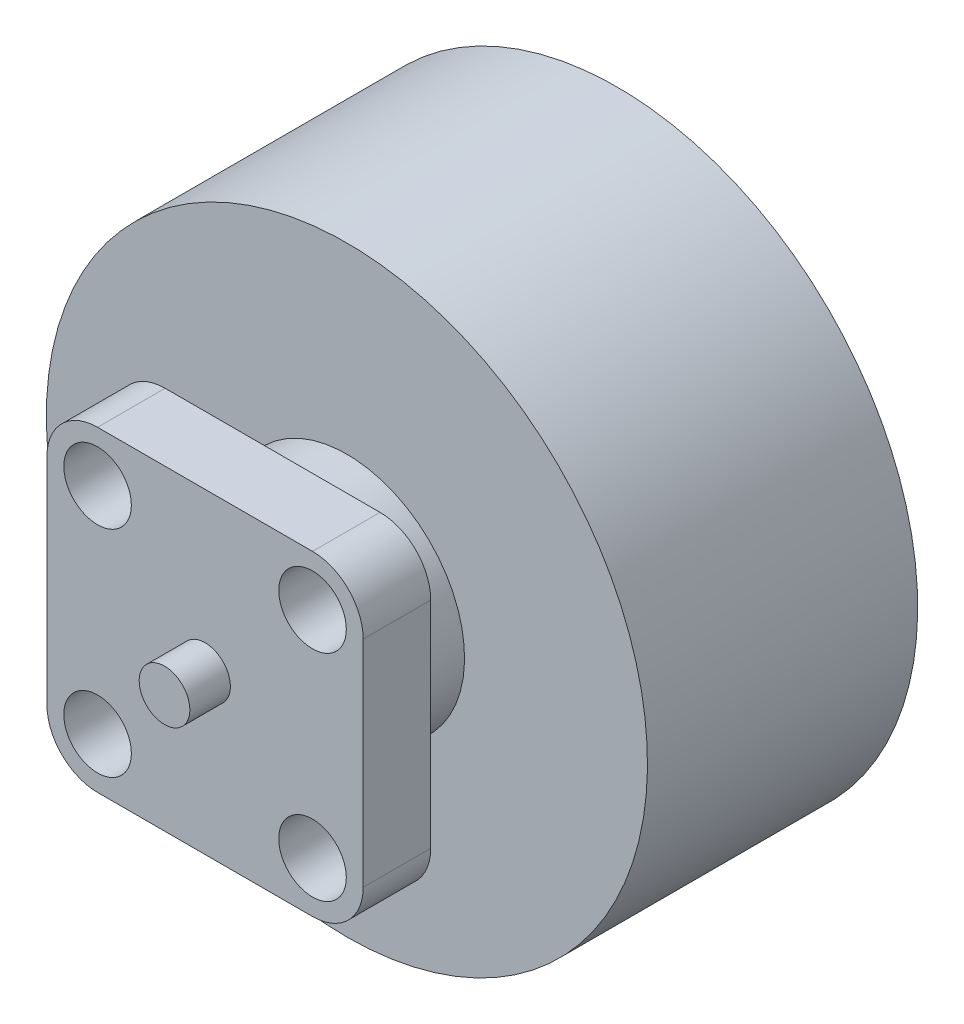
SolidWorks part; units mm, degrees
ref_plane "Front Plane" through (0, 0, 0) normal (0, 0, 1) x (1, 0, 0)
ref_plane "Top Plane" through (0, 0, 0) normal (0, 1, 0) x (1, 0, 0)
ref_plane "Right Plane" through (0, 0, 0) normal (1, 0, 0) x (0, 0, -1)
sketch "Sketch1" plane through (0, 0, 0) normal (1, 0, 0) x (0, 0, -1)
  line L0 (-1.2, 0) -> (16.4, 0)
  line L2 (-1.2, 0.75) -> (16.4, 0.75)
  line L3 (-1.2, 0.75) -> (-1.2, -0.75)
  line L4 (-1.2, -0.75) -> (16.4, -0.75)
  line L5 (16.4, 0.75) -> (16.4, -0.75)
  line L6 (4.2, 0) -> (12.2, 0)
  line L7 (4.2, 0) -> (4.2, 8.9)
  line L8 (4.2, 8.9) -> (12.2, 8.9)
  line L9 (12.2, 0) -> (12.2, 8.9)
  line L10 (0, 0) -> (4.2, 0)
  line L11 (0, 0) -> (0, 3.4836)
  line L12 (0, 3.4836) -> (4.2, 3.4836)
  line L13 (4.2, 0) -> (4.2, 3.4836)
  point P14 (0, 0)
  point P15 (0, 0)
  point P16 (0, 0)
  dimension "D1" = 17.6
  dimension "D2" = 1.5
  dimension "D3" = 1.2
  dimension "D4" = 4.2
  dimension "D5" = 8
  dimension "D6" = 8.9
revolve "Revolve1" add sketch "Sketch1" angle 360 about L0 region at (0, 0.375, 0.6) region at (0, 0.375, -2.1) region at (0, 0.375, -8.2) region at (0, 2.1168, -2.1) region at (0, 0.375, -14.3) region at (0, 4.825, -8.2)
sketch "Sketch2" plane through (0, 0, 0) normal (0, 0, 1) x (1, 0, 0)
  line L1 (0, 0) -> (4.5, 0) construction
  line L3 (-4.682, -4.682) -> (4.682, -4.682)
  line L4 (-4.682, -4.682) -> (-4.682, 4.682)
  line L5 (-4.682, 4.682) -> (4.682, 4.682)
  line L6 (4.682, -4.682) -> (4.682, 4.682)
  line L7 (-4.682, -4.682) -> (4.682, 4.682) construction
  line L8 (-4.682, 4.682) -> (4.682, -4.682) construction
  circle A0 centre (3.182, 3.182) radius 1
  circle A1 centre (0, 0) radius 4.5 construction
  circle A2 centre (3.182, -3.182) radius 1
  circle A3 centre (-3.182, -3.182) radius 1
  circle A4 centre (-3.182, 3.182) radius 1
  point P15 (0, 0)
  point P17 (0, 0)
  point P18 (-2.0934, 3.3438)
  point P19 (0, 0)
  dimension "D1" = 2
  dimension "D2" = 9
  dimension "D3" = 1.5
  dimension "D4" = 4
extrude "Boss-Extrude1" add sketch "Sketch2" against normal blind 2
fillet "Fillet1" radius 1.5 4 edges at (4.682, -4.682, -1) (-4.682, -4.682, -1) (-4.682, 4.682, -1) (4.682, 4.682, -1)
sketch "Sketch3" plane through (0, 0, -12.2) normal (0, 0, -1) x (-1, 0, 0)
  circle A0 centre (0, 2.5) radius 1
  circle A1 centre (0, 0) radius 2.5 construction
  circle A2 centre (2.5, 0) radius 1
  circle A3 centre (0, -2.5) radius 1
  circle A4 centre (-2.5, 0) radius 1
  point P6 (0, 0)
  point P7 (0, 0)
  point P13 (0, 0)
  point P14 (0, 0)
  dimension "D1" = 2
  dimension "D2" = 5
  dimension "D3" = 4
extrude "Cut-Extrude1" cut sketch "Sketch3" against normal blind 2
